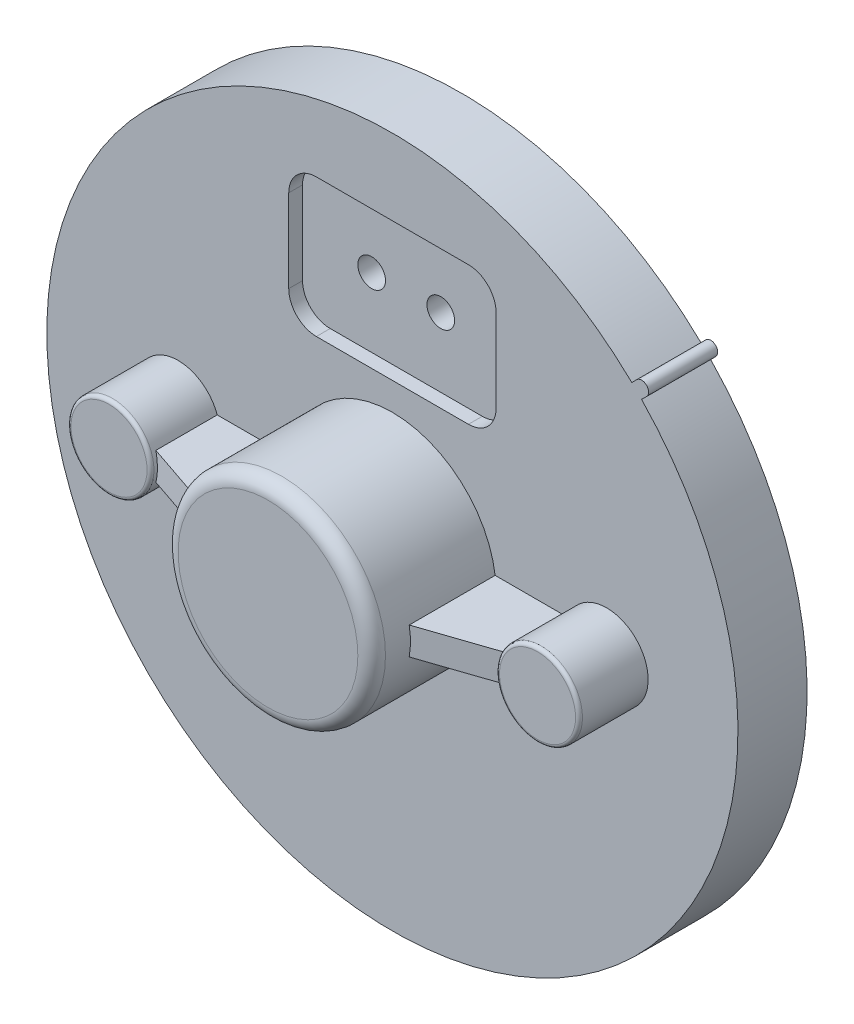
SolidWorks part; units mm, degrees
ref_plane "Спереди" through (0, 0, 0) normal (0, 0, 1) x (1, 0, 0)
ref_plane "Сверху" through (0, 0, 0) normal (0, 1, 0) x (1, 0, 0)
ref_plane "Справа" through (0, 0, 0) normal (1, 0, 0) x (0, 0, -1)
sketch "Эскиз1" plane through (0, 0, 0) normal (0, 0, 1) x (1, 0, 0)
  circle A0 centre (0, 0) radius 25
  dimension "D1" = 50
extrude "Бобышка-Вытянуть1" add sketch "Эскиз1" along normal blind 5
sketch "Эскиз2" plane through (0, 0, 5) normal (0, 0, 1) x (1, 0, 0)
  circle A0 centre (0, 0) radius 7.5
extrude "Бобышка-Вытянуть2" add sketch "Эскиз2" along normal blind 9
sketch "Эскиз3" plane through (0, 0, 5) normal (0, 0, 1) x (1, 0, 0)
  circle A3 centre (15.5, 0) radius 3
  circle A4 centre (-15.5, 0) radius 3
extrude "Бобышка-Вытянуть3" add sketch "Эскиз3" along normal blind 5
fillet "Скругление1" radius 1 1 edges at (7.5, 0, 14)
sketch "Эскиз4" plane through (0, 0, 0) normal (0, 1, 0) x (1, 0, 0)
  line L0 (0, 3.305) -> (0, -17.9765) construction
  line L2 (-15.8893, -8.3507) -> (-5.0119, -12.0391)
  line L11 (-15.8893, -5) -> (-15.8893, -8.3507)
  line L12 (-15.8893, -5) -> (-5.0119, -5)
  line L14 (-5.0119, -12.0391) -> (-5.0119, -5)
  line L15 (5.0119, -12.0391) -> (5.0119, -5)
  line L16 (15.8893, -5) -> (5.0119, -5)
  line L17 (15.8893, -5) -> (15.8893, -8.3507)
  line L18 (15.8893, -8.3507) -> (5.0119, -12.0391)
extrude "Бобышка-Вытянуть4" add sketch "Эскиз4" along normal blind 1 and the other way blind 1
fillet "Скругление2" radius 0.25 2 edges at (-12.5, 0, 10) (18.5, 0, 10)
sketch "Эскиз5" plane through (0, 0, 5) normal (0, 0, 1) x (1, 0, 0)
  line L2 (17.6777, 18.3848) -> (17.0152, 17.7223)
  line L3 (17.0152, 17.7223) -> (17.7092, 17.0284)
  line L4 (17.7092, 17.0284) -> (18.3777, 17.6707)
  arc A1 (18.3777, 17.6707) -> (17.6777, 18.3848) centre (18.0312, 18.0312) ccw
extrude "Бобышка-Вытянуть5" add sketch "Эскиз5" against normal up to surface (5 mm away) up to face at (25, 0, 0)
sketch "Эскиз6" plane through (0, 0, 5) normal (0, 0, 1) x (1, 0, 0)
  line L0 (-5.5, 9.5) -> (5.5, 9.5)
  line L2 (7.5, 11.5) -> (7.5, 17.5)
  line L3 (5.5, 19.5) -> (-5.5, 19.5)
  line L4 (-7.5, 17.5) -> (-7.5, 11.5)
  arc A1 (5.5, 9.5) -> (7.5, 11.5) centre (5.5, 11.5) ccw
  arc A2 (7.5, 17.5) -> (5.5, 19.5) centre (5.5, 17.5) ccw
  arc A3 (-5.5, 19.5) -> (-7.5, 17.5) centre (-5.5, 17.5) ccw
  arc A4 (-7.5, 11.5) -> (-5.5, 9.5) centre (-5.5, 11.5) ccw
  dimension "D1" = 2
extrude "Вырез-Вытянуть1" cut sketch "Эскиз6" against normal blind 1
sketch "Эскиз7" plane through (0, 0, 4) normal (0, 0, 1) x (1, 0, 0)
  line L0 (5.5, 19.5) -> (-5.5, 19.5) construction
  line L1 (-7.5, 17.5) -> (-7.5, 11.5) construction
  line L2 (7.5, 11.5) -> (7.5, 17.5) construction
  circle A0 centre (-2.5, 14.5) radius 1
  circle A1 centre (2.5, 14.5) radius 1
  dimension "D1" = 2
  dimension "D2" = 2
  dimension "D3" = 5
  dimension "D4" = 5
  dimension "D5" = 5
  dimension "D6" = 5
extrude "Вырез-Вытянуть2" cut sketch "Эскиз7" against normal blind 21
